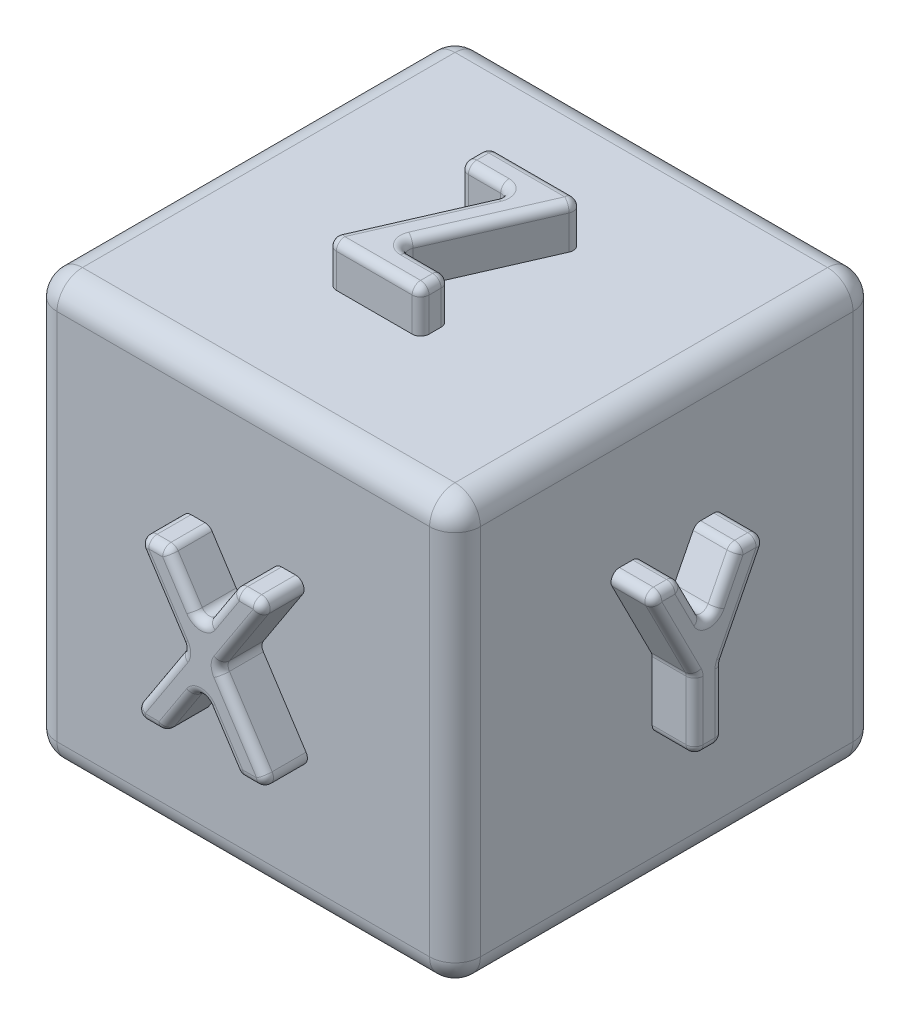
SolidWorks part; units mm, degrees
ref_plane "Front Plane" through (0, 0, 0) normal (0, 0, 1) x (1, 0, 0)
ref_plane "Top Plane" through (0, 0, 0) normal (0, 1, 0) x (1, 0, 0)
ref_plane "Right Plane" through (0, 0, 0) normal (1, 0, 0) x (0, 0, -1)
sketch "Sketch1" plane through (0, 0, 0) normal (0, 1, 0) x (1, 0, 0)
  line L1 (-25, 25) -> (25, 25)
  line L2 (-25, 25) -> (-25, -25)
  line L3 (-25, -25) -> (25, -25)
  line L4 (25, 25) -> (25, -25)
  line L5 (-25, 25) -> (25, -25) construction
  line L6 (-25, -25) -> (25, 25) construction
  point P0 (0, 0)
  dimension "D1" = 50
extrude "Boss-Extrude1" add sketch "Sketch1" along normal blind 50
sketch "Sketch2" plane through (0, 0, 25) normal (0, 0, 1) x (1, 0, 0)
  line L0 (0, 50) -> (0, 0) construction
  line L1 (-25, 50) -> (25, 50) construction
  line L2 (-25, 25) -> (25.0535, 25) construction
  line L3 (-25, 50) -> (-25, 0) construction
  line L4 (-8.0156, 34.1403) -> (-3.9857, 34.1403)
  line L5 (-3.9857, 34.1403) -> (-0.0055, 28.0231)
  line L6 (-0.0055, 28.0231) -> (3.9823, 34.1403)
  line L7 (3.9823, 34.1403) -> (8.0159, 34.1403)
  line L8 (8.0159, 34.1403) -> (2.0094, 24.9283)
  line L9 (2.0094, 24.9283) -> (8.4128, 15.0903)
  line L10 (8.4128, 15.0903) -> (4.383, 15.0903)
  line L11 (4.383, 15.0903) -> (-0.0055, 21.8372)
  line L12 (-0.0055, 21.8372) -> (-4.4055, 15.0903)
  line L13 (-4.4055, 15.0903) -> (-8.4391, 15.0903)
  line L14 (-8.4391, 15.0903) -> (-2.0205, 24.9321)
  line L15 (-2.0205, 24.9321) -> (-8.0156, 34.1403)
extrude "Boss-Extrude2" add sketch "Sketch2" along normal blind 5
sketch "Sketch3" plane through (25, 0, 0) normal (1, 0, 0) x (0, 0, -1)
  line L0 (0, 50) -> (0, 0) construction
  line L1 (-25, 50) -> (25, 50) construction
  line L2 (-25, 25) -> (25, 25) construction
  line L3 (-25, 50) -> (-25, 0) construction
  line L4 (25, 50) -> (25, 0) construction
  line L5 (-7.206, 34.604) -> (-3.4014, 34.604)
  line L6 (-3.4014, 34.604) -> (-0.0012, 27.922)
  line L7 (-0.0012, 27.922) -> (3.3989, 34.604)
  line L8 (3.3989, 34.604) -> (7.2036, 34.604)
  line L9 (7.2036, 34.604) -> (1.7084, 23.8044)
  line L10 (1.7084, 23.8044) -> (1.7084, 15.554)
  line L11 (1.7084, 15.554) -> (-1.7108, 15.554)
  line L12 (-1.7108, 15.554) -> (-1.7108, 23.8044)
  line L13 (-1.7108, 23.8044) -> (-7.206, 34.604)
extrude "Boss-Extrude3" add sketch "Sketch3" along normal blind 5
sketch "Sketch4" plane through (0, 50, 0) normal (0, 1, 0) x (1, 0, 0)
  line L0 (0, 25) -> (0, -25) construction
  line L3 (-25, 0) -> (24.9828, 0) construction
  line L7 (25, 25) -> (-25, 25) construction
  line L8 (-25, -25) -> (25, -25) construction
  line L9 (-25, 25) -> (-25, -25) construction
  line L10 (-5.7099, 9.7114) -> (5.769, 9.7114)
  line L11 (5.769, 9.7114) -> (-1.0542, -5.9194)
  line L12 (-1.0542, -5.9194) -> (5.2805, -5.9194)
  line L13 (5.2805, -5.9194) -> (5.2805, -9.3386)
  line L14 (5.2805, -9.3386) -> (-6.1983, -9.3386)
  line L15 (-6.1983, -9.3386) -> (0.6287, 6.2921)
  line L16 (0.6287, 6.2921) -> (-5.7099, 6.2921)
  line L17 (-5.7099, 6.2921) -> (-5.7099, 9.7114)
  point P3 (0, 0)
  point P5 (0, 0)
  point P9 (0, 0)
  point P10 (0, 0)
  point P11 (0, 0)
  point P12 (0, 0)
  point P13 (0, 0)
  point P14 (0, 0)
  point P17 (0, 0)
  point P20 (0, 0)
  point P21 (24.9828, 0)
extrude "Boss-Extrude4" add sketch "Sketch4" along normal blind 5
sketch "Sketch6" plane through (0, 0, -25) normal (0, 0, -1) x (-1, 0, 0)
  line L12 (-8.4128, 15.0903) -> (-4.383, 15.0903)
  line L13 (-4.383, 15.0903) -> (0.0055, 21.8372)
  line L14 (0.0055, 21.8372) -> (4.4055, 15.0903)
  line L15 (4.4055, 15.0903) -> (8.4391, 15.0903)
  line L16 (8.4391, 15.0903) -> (2.0205, 24.9321)
  line L17 (2.0205, 24.9321) -> (8.0156, 34.1403)
  line L18 (8.0156, 34.1403) -> (3.9857, 34.1403)
  line L19 (3.9857, 34.1403) -> (0.0055, 28.0231)
  line L20 (0.0055, 28.0231) -> (-3.9823, 34.1403)
  line L21 (-3.9823, 34.1403) -> (-8.0159, 34.1403)
  line L22 (-8.0159, 34.1403) -> (-2.0094, 24.9283)
  line L23 (-2.0094, 24.9283) -> (-8.4128, 15.0903)
  line L24 (-8.4128, 15.0903) -> (-4.383, 15.0903)
  line L25 (-4.383, 15.0903) -> (0.0055, 21.8372)
  line L26 (0.0055, 21.8372) -> (4.4055, 15.0903)
  line L27 (4.4055, 15.0903) -> (8.4391, 15.0903)
  line L28 (8.4391, 15.0903) -> (2.0205, 24.9321)
  line L29 (2.0205, 24.9321) -> (8.0156, 34.1403)
  line L30 (8.0156, 34.1403) -> (3.9857, 34.1403)
  line L31 (3.9857, 34.1403) -> (0.0055, 28.0231)
  line L32 (0.0055, 28.0231) -> (-3.9823, 34.1403)
  line L33 (-3.9823, 34.1403) -> (-8.0159, 34.1403)
  line L34 (-8.0159, 34.1403) -> (-2.0094, 24.9283)
  line L35 (-2.0094, 24.9283) -> (-8.4128, 15.0903)
  dimension "D1" = 0
extrude "Cut-Extrude3" cut sketch "Sketch6" against normal blind 5
sketch "Sketch7" plane through (-25, 0, 0) normal (-1, 0, 0) x (0, 0, 1)
  line L9 (-7.2036, 34.604) -> (-1.7084, 23.8044)
  line L10 (-1.7084, 23.8044) -> (-1.7084, 15.554)
  line L11 (-1.7084, 15.554) -> (1.7108, 15.554)
  line L12 (1.7108, 15.554) -> (1.7108, 23.8044)
  line L13 (1.7108, 23.8044) -> (7.206, 34.604)
  line L14 (7.206, 34.604) -> (3.4014, 34.604)
  line L15 (3.4014, 34.604) -> (0.0012, 27.922)
  line L16 (0.0012, 27.922) -> (-3.3989, 34.604)
  line L17 (-3.3989, 34.604) -> (-7.2036, 34.604)
  line L18 (-7.2036, 34.604) -> (-1.7084, 23.8044)
  line L19 (-1.7084, 23.8044) -> (-1.7084, 15.554)
  line L20 (-1.7084, 15.554) -> (1.7108, 15.554)
  line L21 (1.7108, 15.554) -> (1.7108, 23.8044)
  line L22 (1.7108, 23.8044) -> (7.206, 34.604)
  line L23 (7.206, 34.604) -> (3.4014, 34.604)
  line L24 (3.4014, 34.604) -> (0.0012, 27.922)
  line L25 (0.0012, 27.922) -> (-3.3989, 34.604)
  line L26 (-3.3989, 34.604) -> (-7.2036, 34.604)
  dimension "D1" = 0
extrude "Cut-Extrude4" cut sketch "Sketch7" against normal blind 5
sketch "Sketch8" plane through (0, 0, 0) normal (0, -1, 0) x (1, 0, 0)
  line L8 (-5.7099, -9.7114) -> (5.769, -9.7114)
  line L9 (5.769, -9.7114) -> (-1.0542, 5.9194)
  line L10 (-1.0542, 5.9194) -> (5.2805, 5.9194)
  line L11 (5.2805, 5.9194) -> (5.2805, 9.3386)
  line L12 (5.2805, 9.3386) -> (-6.1983, 9.3386)
  line L13 (-6.1983, 9.3386) -> (0.6287, -6.2921)
  line L14 (0.6287, -6.2921) -> (-5.7099, -6.2921)
  line L15 (-5.7099, -6.2921) -> (-5.7099, -9.7114)
  line L16 (-5.7099, -9.7114) -> (5.769, -9.7114)
  line L17 (5.769, -9.7114) -> (-1.0542, 5.9194)
  line L18 (-1.0542, 5.9194) -> (5.2805, 5.9194)
  line L19 (5.2805, 5.9194) -> (5.2805, 9.3386)
  line L20 (5.2805, 9.3386) -> (-6.1983, 9.3386)
  line L21 (-6.1983, 9.3386) -> (0.6287, -6.2921)
  line L22 (0.6287, -6.2921) -> (-5.7099, -6.2921)
  line L23 (-5.7099, -6.2921) -> (-5.7099, -9.7114)
  dimension "D1" = 0
extrude "Cut-Extrude5" cut sketch "Sketch8" against normal blind 5
fillet "Fillet2" radius 1 116 edges at (-6.0007, 34.1403, 30) (-1.9956, 31.0817, 30) (1.9884, 31.0817, 30) (5.9991, 34.1403, 30) (5.0126, 29.5343, 30) (5.2111, 20.0093, 30) (6.3979, 15.0903, 30) (2.1887, 18.4638, 30) (-2.2055, 18.4638, 30) (-6.4223, 15.0903, 30) (-5.2298, 20.0112, 30) (-5.018, 29.5362, 30) (-0.0055, 21.8372, 27.5) (-8.4391, 15.0903, 27.5) (4.383, 15.0903, 27.5) (-2.0205, 24.9321, 27.5) (-0.0055, 28.0231, 27.5) (8.4128, 15.0903, 27.5) (-4.4055, 15.0903, 27.5) (2.0094, 24.9283, 27.5) (8.0159, 34.1403, 27.5) (3.9823, 34.1403, 27.5) (-8.0156, 34.1403, 27.5) (-3.9857, 34.1403, 27.5) (0.0296, 55, -9.7114) (2.3574, 55, -1.896) (2.1132, 55, 5.9194) (5.2805, 55, 7.629) (-0.4589, 55, 9.3386) (-2.7848, 55, 1.5232) (-2.5406, 55, -6.2921) (-5.7099, 55, -8.0018) (30, 34.604, 5.3037) (30, 31.263, 1.7013) (30, 31.263, -1.6989) (30, 34.604, -5.3013) (30, 29.2042, -4.456) (30, 19.6792, -1.7084) (30, 15.554, 0.0012) (30, 19.6792, 1.7108) (30, 29.2042, 4.4584) (-2.5406, 5, -6.2921) (-2.7848, 5, 1.5232) (-0.4589, 5, 9.3386) (5.2805, 5, 7.629) (2.1132, 5, 5.9194) (2.3574, 5, -1.896) (0.0296, 5, -9.7114) (-5.7099, 5, -8.0018) (-20, 31.263, -1.6989) (-20, 31.263, 1.7013) (-20, 34.604, 5.3037) (-20, 29.2042, 4.4584) (-20, 19.6792, 1.7108) (-20, 15.554, 0.0012) (-20, 19.6792, -1.7084) (-20, 29.2042, -4.456) (-20, 34.604, -5.3013) (5.0126, 29.5343, -20) (5.9991, 34.1403, -20) (1.9884, 31.0817, -20) (-1.9956, 31.0817, -20) (-6.0007, 34.1403, -20) (-5.018, 29.5362, -20) (-5.2298, 20.0112, -20) (-6.4223, 15.0903, -20) (-2.2055, 18.4638, -20) (2.1887, 18.4638, -20) (6.3979, 15.0903, -20) (5.2111, 20.0093, -20) (5.769, 2.5, -9.7114) (5.2805, 2.5, 5.9194) (5.2805, 2.5, 9.3386) (-6.1983, 2.5, 9.3386) (-5.7099, 2.5, -9.7114) (-5.7099, 2.5, -6.2921) (0.6287, 2.5, -6.2921) (-1.0542, 2.5, 5.9194) (-22.5, 15.554, 1.7108) (-22.5, 23.8044, 1.7108) (-22.5, 34.604, -3.3989) (-22.5, 34.604, 7.206) (-22.5, 34.604, 3.4014) (-22.5, 34.604, -7.2036) (-22.5, 27.922, 0.0012) (-22.5, 15.554, -1.7084) (-22.5, 23.8044, -1.7084) (-8.0156, 34.1403, -22.5) (8.0159, 34.1403, -22.5) (-3.9857, 34.1403, -22.5) (3.9823, 34.1403, -22.5) (-2.0205, 24.9321, -22.5) (-0.0055, 28.0231, -22.5) (2.0094, 24.9283, -22.5) (8.4128, 15.0903, -22.5) (4.383, 15.0903, -22.5) (-0.0055, 21.8372, -22.5) (-4.4055, 15.0903, -22.5) (-8.4391, 15.0903, -22.5) (5.2805, 52.5, 5.9194) (-1.0542, 52.5, 5.9194) (5.2805, 52.5, 9.3386) (-6.1983, 52.5, 9.3386) (0.6287, 52.5, -6.2921) (5.769, 52.5, -9.7114) (-5.7099, 52.5, -6.2921) (-5.7099, 52.5, -9.7114) (27.5, 23.8044, 1.7108) (27.5, 15.554, -1.7084) (27.5, 15.554, 1.7108) (27.5, 23.8044, -1.7084) (27.5, 34.604, -7.2036) (27.5, 34.604, -3.3989) (27.5, 27.922, 0.0012) (27.5, 34.604, 7.206) (27.5, 34.604, 3.4014)
fillet "Fillet3" radius 3 12 edges at (25, 50, 0) (25, 25, -25) (0, 50, -25) (0, 0, -25) (25, 0, 0) (25, 25, 25) (-25, 25, -25) (-25, 50, 0) (0, 50, 25) (0, 0, 25) (-25, 0, 0) (-25, 25, 25)
